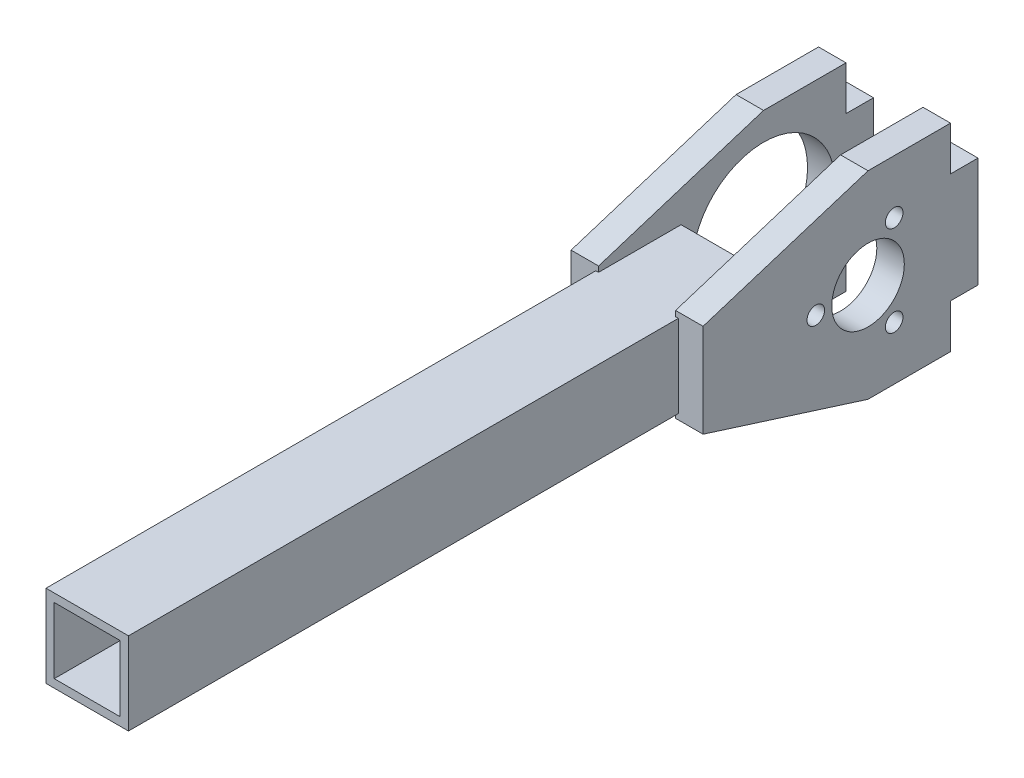
SolidWorks part; units mm, degrees
ref_plane "正面" through (0, 0, 0) normal (0, 0, 1) x (1, 0, 0)
ref_plane "平面" through (0, 0, 0) normal (0, 1, 0) x (1, 0, 0)
ref_plane "右側面" through (0, 0, 0) normal (1, 0, 0) x (0, 0, -1)
sketch "ｽｹｯﾁ1" plane through (0, 0, 0) normal (0, 0, 1) x (1, 0, 0)
  circle A0 centre (0, 0) radius 23.5 construction
  circle A1 centre (0, 0) radius 20 construction
  circle A2 centre (0, 20) radius 1.6 construction
  circle A3 centre (20, 0) radius 1.6 construction
  circle A4 centre (0, -20) radius 1.6 construction
  circle A5 centre (-20, 0) radius 1.6 construction
  point P15 (0, 0)
  dimension "D1" = 40
  dimension "47" = 47
  dimension "D2" = 3.2
  dimension "D3" = 4
ref_plane "arm_link1_m2006_mount_surface" through (7, 0, 0) normal (1, 0, 0) x (0, 0, -1)
ref_plane "arm_link1_axis_hold_mount_surface" through (-7, 0, 0) normal (1, 0, 0) x (0, 0, -1)
sketch "ｽｹｯﾁ3" plane through (7, 0, 0) normal (1, 0, 0) x (0, 0, -1)
  line L0 (0, 0) -> (-45, 0) construction
  line L1 (5, 10) -> (5, -10)
  line L2 (5, -10) -> (0, -10)
  line L3 (0, -10) -> (0, -18)
  line L4 (0, -18) -> (-15, -18)
  line L5 (-15, -18) -> (-45, -8.5)
  line L6 (-45, -8.5) -> (-45, 8.5)
  line L7 (-15, 18) -> (-45, 8.5)
  line L8 (0, 18) -> (-15, 18)
  line L9 (0, 10) -> (0, 18)
  line L10 (5, 10) -> (0, 10)
  circle A0 centre (-15, 0) radius 9.5 construction
  circle A1 centre (-15, 0) radius 6.6
  circle A2 centre (-24.5, 0) radius 1.6
  circle A3 centre (-10.25, 8.2272) radius 1.6
  circle A4 centre (-10.25, -8.2272) radius 1.6
  point P17 (5, 0)
  point P26 (-15, 0)
  dimension "D7" = 19
  dimension "D8" = 13.2
  dimension "D9" = 3.2
  dimension "D1" = 8.5
  dimension "D2" = 10
  dimension "D3" = 8
  dimension "D4" = 15
  dimension "D5" = 45
  dimension "D6" = 5
  dimension "D10" = 3
extrude "ﾎﾞｽ - 押し出し1" add sketch "ｽｹｯﾁ3" along normal blind 5
sketch "ｽｹｯﾁ5" plane through (-7, 0, 0) normal (1, 0, 0) x (0, 0, -1)
  line L0 (0, 0) -> (-53.7832, 0) construction
  line L1 (-45, -8.5) -> (-45, 8.5)
  line L2 (-45, 8.5) -> (-15, 18)
  line L3 (-15, 18) -> (0, 18)
  line L4 (0, 18) -> (0, 10)
  line L5 (0, 10) -> (5, 10)
  line L6 (5, 10) -> (5, -10)
  line L8 (-45, 8.5) -> (-45, -8.5) construction
  line L9 (0, -10) -> (5, -10)
  line L10 (0, -18) -> (0, -10)
  line L11 (-15, -18) -> (0, -18)
  line L12 (-45, -8.5) -> (-15, -18)
  circle A0 centre (-15, 0) radius 13
  point P19 (5, 0)
  point P23 (-45, 0)
  dimension "D6" = 26
  dimension "D1" = 5
  dimension "D2" = 10
  dimension "D3" = 8
  dimension "D4" = 8.5
  dimension "D5" = 15
extrude "ﾎﾞｽ - 押し出し2" add sketch "ｽｹｯﾁ5" against normal blind 5 separate body
sketch "ｽｹｯﾁ6" plane through (0, 0, 45) normal (0, 0, 1) x (1, 0, 0)
  line L1 (7.5, -7.5) -> (-7.5, -7.5)
  line L2 (7.5, -7.5) -> (7.5, 7.5)
  line L3 (7.5, 7.5) -> (-7.5, 7.5)
  line L4 (-7.5, -7.5) -> (-7.5, 7.5)
  line L6 (0, -25.85) -> (0, 25.85) construction
  line L7 (25.85, 0) -> (-25.85, 0) construction
  line L8 (6, -6) -> (-6, -6)
  line L9 (-6, -6) -> (-6, 6)
  line L10 (6, 6) -> (-6, 6)
  line L11 (6, -6) -> (6, 6)
  dimension "D1" = 15
  dimension "D2" = 7.5
  dimension "D3" = 7.5
  dimension "D4" = 1.5
extrude "ﾎﾞｽ - 押し出し3" add sketch "ｽｹｯﾁ6" against normal blind 15 and the other way blind 100
